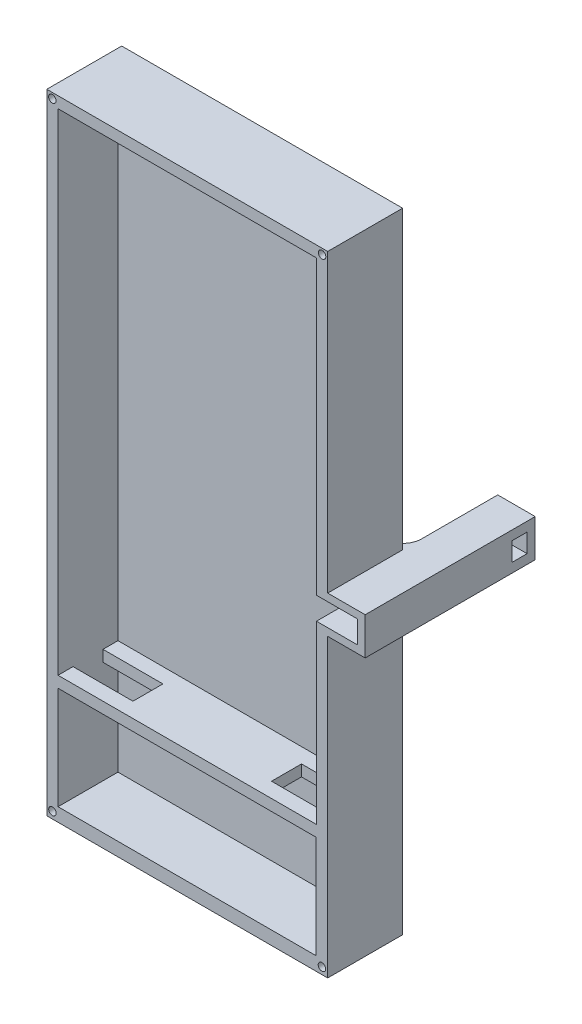
SolidWorks part; units mm, degrees
ref_plane "Front Plane" through (0, 0, 0) normal (0, 0, 1) x (1, 0, 0)
ref_plane "Top Plane" through (0, 0, 0) normal (0, 1, 0) x (1, 0, 0)
ref_plane "Right Plane" through (0, 0, 0) normal (1, 0, 0) x (0, 0, -1)
sketch "Sketch1" plane through (0, 0, 0) normal (0, 0, 1) x (1, 0, 0)
  line L1 (-37.5, -84) -> (37.5, -84)
  line L2 (-37.5, -84) -> (-37.5, 84)
  line L3 (-37.5, 84) -> (37.5, 84)
  line L4 (37.5, -84) -> (37.5, 84)
  line L5 (-37.5, -84) -> (37.5, 84) construction
  line L6 (-37.5, 84) -> (37.5, -84) construction
  point P0 (0, 0)
  dimension "D1" = 168
  dimension "D2" = 75
extrude "Boss-Extrude1" add sketch "Sketch1" along normal blind 20
sketch "Sketch2" plane through (37.5, 0, 0) normal (1, 0, 0) x (0, 0, -1)
  line L0 (0, -84) -> (0, 84) construction
  line L8 (0, 5) -> (25.4, 5)
  line L9 (0, -5) -> (25.4, -5)
  line L11 (25.4, -5) -> (25.4, 5)
  line L12 (0, 5) -> (-20, 5)
  line L13 (-20, -84) -> (-20, 84) construction
  line L14 (-20, 5) -> (-20, -5)
  line L15 (-20, -5) -> (0, -5)
  point P0 (0, 0)
  dimension "D3" = 25.4
  dimension "D4" = 25.4
extrude "Boss-Extrude2" add sketch "Sketch2" along normal blind 10 separate body
sketch "Sketch3" plane through (0, 0, 20) normal (0, 0, 1) x (1, 0, 0)
  line L1 (37.5, -5) -> (47.5, 5) construction
  line L4 (37.5, 5) -> (47.5, -5) construction
  line L14 (39.5, -3) -> (45.5, -3)
  line L15 (39.5, -3) -> (39.5, 3)
  line L16 (39.5, 3) -> (45.5, 3)
  line L17 (45.5, -3) -> (45.5, 3)
  line L18 (39.5, -3) -> (45.5, 3) construction
  line L19 (39.5, 3) -> (45.5, -3) construction
  point P2 (42.5, 0)
  dimension "D1" = 6
extrude "Cut-Extrude2" cut sketch "Sketch3" against normal blind 39.37
sketch "Sketch6" plane through (47.5, 0, 0) normal (1, 0, 0) x (0, 0, -1)
  line L3 (19.2304, -2.5) -> (23.2304, -2.5)
  line L10 (19.2304, -2.5) -> (19.2304, 2.5)
  line L11 (19.2304, 2.5) -> (23.2304, 2.5)
  line L12 (25.4, -5) -> (25.4, 5) construction
  line L13 (25.4, 0) -> (25.4, 2.5) construction
  line L14 (25.4, 0) -> (25.4, -2.5) construction
  line L15 (23.2304, -2.5) -> (23.2304, 2.5)
  line L16 (19.2304, -2.5) -> (23.2304, 2.5) construction
  line L17 (19.2304, 2.5) -> (23.2304, -2.5) construction
  point P5 (21.2304, 0)
  point P6 (21.2304, 0)
  dimension "D2" = 4
  dimension "D3" = 5
  dimension "D4" = 2.5
  dimension "D6" = 2.5
extrude "Cut-Extrude4" cut sketch "Sketch6" against normal blind 5
sketch "Sketch7" plane through (0, 0, 20) normal (0, 0, 1) x (1, 0, 0)
  line L0 (37.5, 84) -> (34.5, 84) construction
  line L1 (37.5, 84) -> (-37.5, 84) construction
  line L2 (34.5, 84) -> (34.5, 81) construction
  line L3 (34.5, 81) -> (34.5, -50)
  line L5 (-34.5, -50) -> (-34.5, 81)
  line L6 (-34.5, 81) -> (34.5, 81)
  line L7 (34.5, -50) -> (34.5, 81)
  line L10 (34.5, -50) -> (-34.5, -50)
  point P6 (0, 0)
  dimension "D1" = 3
  dimension "D2" = 3
  dimension "D3" = 131
extrude "Cut-Extrude5" cut sketch "Sketch7" against normal blind 16 contours L10 L3 L6 L5 region at (0, 15.5, 20)
sketch "Sketch8" plane through (0, 0, 20) normal (0, 0, 1) x (1, 0, 0)
  line L2 (-34.5, -53) -> (34.4246, -53)
  line L3 (-34.5, -53) -> (-34.5, -80.4)
  line L4 (-34.5, -80.4) -> (34.4246, -80.4)
  line L5 (34.4246, -53) -> (34.4246, -80.4)
  dimension "D2" = 27.4
extrude "Cut-Extrude6" cut sketch "Sketch8" against normal blind 16
sketch "Sketch9" plane through (0, -50, 0) normal (0, 1, 0) x (1, 0, 0)
  line L0 (-34.5, -20) -> (-34.5, -16) construction
  line L1 (-34.5, -4) -> (-34.5, -20) construction
  line L2 (-34.5, -4) -> (-34.5, -8) construction
  line L3 (0, 0) -> (0, -21.8298) construction
  line L4 (-34.5, -8) -> (-18.5, -8)
  line L5 (-34.5, -8) -> (-34.5, -16)
  line L6 (-34.5, -16) -> (-18.5, -16)
  line L7 (-18.5, -8) -> (-18.5, -16)
  line L9 (18.5, -8) -> (18.5, -16)
  line L12 (18.5, -8) -> (34.5, -8)
  line L13 (34.5, -4) -> (34.5, -20) construction
  line L14 (34.5, -8) -> (34.5, -16)
  line L15 (34.5, -16) -> (18.5, -16)
  dimension "D1" = 4
  dimension "D2" = 4
  dimension "D3" = 16
extrude "Cut-Extrude7" cut sketch "Sketch9" against normal blind 16
sketch "Sketch10" plane through (0, -50, 0) normal (0, 1, 0) x (1, 0, 0)
  line L0 (0, 0) -> (0, -26.8234) construction
sketch "Sketch11" plane through (0, 0, 20) normal (0, 0, 1) x (1, 0, 0)
  line L1 (39.5, 3) -> (32.0428, 3)
  line L2 (39.5, 3) -> (39.5, -3)
  line L3 (39.5, -3) -> (32.0428, -3)
  line L4 (32.0428, 3) -> (32.0428, -3)
extrude "Cut-Extrude8" cut sketch "Sketch11" against normal blind 16
sketch "Sketch12" plane through (0, -5, 0) normal (0, -1, 0) x (1, 0, 0)
  line L4 (32.42, 0) -> (37.5, 0)
  line L5 (37.5, 0) -> (37.5, -5.08)
  arc A0 (32.42, 0) -> (37.5, -5.08) centre (32.42, -5.08) cw
  point P10 (37.5, 0)
  dimension "D3" = 5.08
extrude "Boss-Extrude3" add sketch "Sketch12" against normal blind 10
fillet "Fillet4" radius 5.08 1 edges at (39.5, 0, 4)
fillet "Fillet5" radius 2.2 1 edges at (42.5, 0, -19.37)
sketch "Sketch13" plane through (0, 0, 0) normal (0, 0, -1) x (-1, 0, 0)
  line L0 (0, 0) -> (0, 84)
  line L1 (-37.5, 84) -> (37.5, 84) construction
  line L2 (0, 0) -> (0, -84)
  line L3 (37.5, -84) -> (-37.5, -84) construction
  line L4 (-63.1649, 0) -> (63.1649, 0) construction
  line L5 (-3.5, 33) -> (3.5, 33)
  line L6 (-3.5, 33) -> (-3.5, 51)
  line L7 (-3.5, 51) -> (3.5, 51)
  line L8 (3.5, 33) -> (3.5, 51)
  line L9 (-3.5, 33) -> (3.5, 51) construction
  line L10 (-3.5, 51) -> (3.5, 33) construction
  line L11 (-3.5, -51) -> (3.5, -51)
  line L12 (3.5, -33) -> (3.5, -51)
  line L13 (-3.5, -33) -> (3.5, -33)
  line L14 (-3.5, -33) -> (-3.5, -51)
  point P5 (0, 42)
  point P15 (0, 0)
  dimension "D1" = 7
  dimension "D2" = 18
extrude "Boss-Extrude4" add sketch "Sketch13" along normal blind 8 contours L7 L8 L5 L6 | L11 L12 L13 L14
sketch "Sketch14" plane through (3.5, 0, 0) normal (1, 0, 0) x (0, 0, -1)
  line L0 (8, 51) -> (4, 51)
  line L1 (8, 51) -> (0, 51) construction
  line L2 (4, 51) -> (4, 42)
  line L4 (3, 35.75) -> (5, 35.75)
  line L5 (3, 35.75) -> (3, 48.25)
  line L6 (3, 48.25) -> (5, 48.25)
  line L7 (5, 35.75) -> (5, 48.25)
  line L8 (3, 35.75) -> (5, 48.25) construction
  line L9 (3, 48.25) -> (5, 35.75) construction
  dimension "D1" = 12.5
  dimension "D2" = 2
extrude "Cut-Extrude9" cut sketch "Sketch14" against normal through all contours L4 L7 L6 L5 region at (3.5, 42, -3.1266)
sketch "Sketch15" plane through (3.5, 0, 0) normal (1, 0, 0) x (0, 0, -1)
  line L0 (8, -33) -> (4, -33)
  line L1 (8, -33) -> (0, -33) construction
  line L2 (4, -33) -> (4, -42)
  line L4 (3, -48.25) -> (5, -48.25)
  line L5 (3, -48.25) -> (3, -35.75)
  line L6 (3, -35.75) -> (5, -35.75)
  line L7 (5, -48.25) -> (5, -35.75)
  line L8 (3, -48.25) -> (5, -35.75) construction
  line L9 (3, -35.75) -> (5, -48.25) construction
  dimension "D1" = 12.5
  dimension "D2" = 2
extrude "Cut-Extrude10" cut sketch "Sketch15" against normal through all contours L7 L6 L5 L4
sketch "Sketch17" plane through (0, 0, 20) normal (0, 0, 1) x (1, 0, 0)
  circle A0 centre (-36.0346, 82.5346) radius 1
  circle A1 centre (36, 82.5) radius 1
  circle A2 centre (35.9623, -82.2) radius 1
  circle A3 centre (-36, -82.2) radius 1
  dimension "D1" = 2
  dimension "D2" = 2
  dimension "D3" = 2
extrude "Cut-Extrude11" cut sketch "Sketch17" against normal blind 2 contours A0 | A1 | A2 | A3
